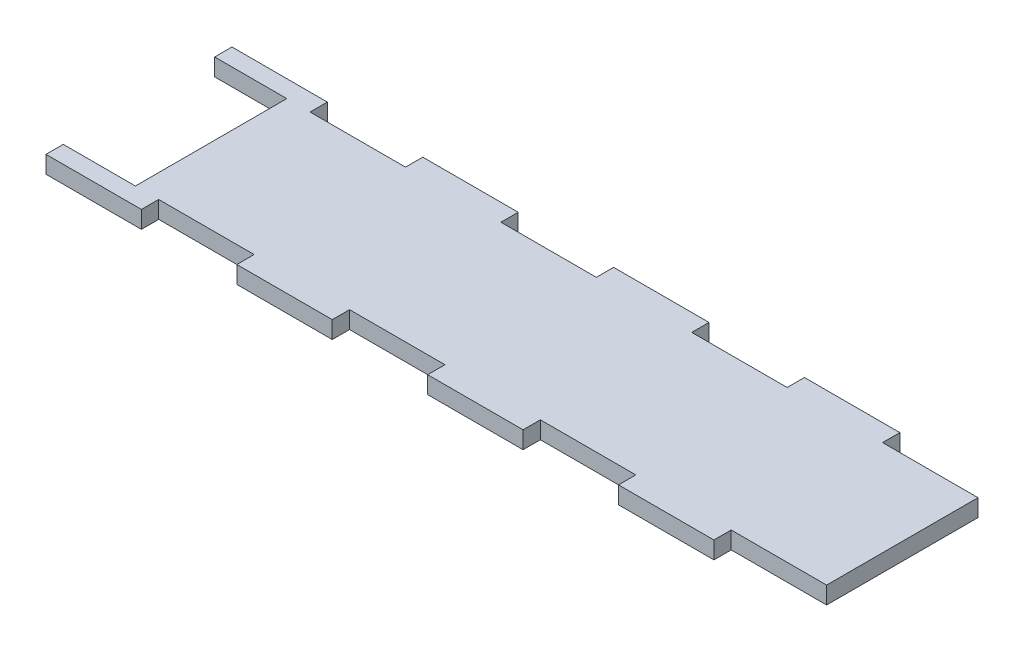
SolidWorks part; units mm, degrees
ref_plane "Front Plane" through (0, 0, 0) normal (0, 0, 1) x (1, 0, 0)
ref_plane "Top Plane" through (0, 0, 0) normal (0, 1, 0) x (1, 0, 0)
ref_plane "Right Plane" through (0, 0, 0) normal (1, 0, 0) x (0, 0, -1)
sketch "Sketch1" plane through (0, 0, 0) normal (0, 1, 0) x (1, 0, 0)
  line L1 (0, 0) -> (228.6, 0)
  line L2 (0, 0) -> (0, 49.5)
  line L3 (0, 49.5) -> (228.6, 49.5)
  line L4 (228.6, 0) -> (228.6, 49.5)
  line L5 (0, 0) -> (228.6, 49.5) construction
  line L6 (0, 49.5) -> (228.6, 0) construction
  point P4 (114.3, 24.75)
  dimension "D1" = 228.6
  dimension "D2" = 49.5
extrude "Boss-Extrude1" add sketch "Sketch1" along normal blind 4.6
sketch "Sketch3" plane through (0, 4.6, 0) normal (0, 1, 0) x (1, 0, 0)
  line L0 (0, 0) -> (228.6, 0) construction
  line L1 (0, 4.6) -> (25.4, 4.6)
  line L2 (0, 4.6) -> (0, 0)
  line L3 (0, 0) -> (25.4, 0)
  line L4 (25.4, 4.6) -> (25.4, 0)
  line L5 (0, 4.6) -> (25.4, 0) construction
  line L6 (0, 0) -> (25.4, 4.6) construction
  line L7 (50.8, 4.6) -> (76.2, 4.6)
  line L8 (50.8, 4.6) -> (50.8, 0)
  line L9 (50.8, 0) -> (76.2, 0)
  line L10 (76.2, 4.6) -> (76.2, 0)
  line L11 (50.8, 4.6) -> (76.2, 0) construction
  line L12 (50.8, 0) -> (76.2, 4.6) construction
  line L13 (101.6, 4.6) -> (127, 4.6)
  line L14 (101.6, 4.6) -> (101.6, 0)
  line L15 (101.6, 0) -> (127, 0)
  line L16 (127, 4.6) -> (127, 0)
  line L17 (101.6, 4.6) -> (127, 0) construction
  line L18 (101.6, 0) -> (127, 4.6) construction
  line L19 (177.8, 4.6) -> (152.4, 4.6)
  line L20 (177.8, 4.6) -> (177.8, 0)
  line L21 (177.8, 0) -> (152.4, 0)
  line L22 (152.4, 4.6) -> (152.4, 0)
  line L23 (177.8, 4.6) -> (152.4, 0) construction
  line L24 (177.8, 0) -> (152.4, 4.6) construction
  line L25 (203.2, 4.6) -> (228.6, 4.6)
  line L26 (203.2, 4.6) -> (203.2, 0)
  line L27 (203.2, 0) -> (228.6, 0)
  line L28 (228.6, 4.6) -> (228.6, 0)
  line L29 (203.2, 4.6) -> (228.6, 0) construction
  line L30 (203.2, 0) -> (228.6, 4.6) construction
  line L31 (0, 49.5) -> (0, 0) construction
  line L32 (228.6, 0) -> (228.6, 49.5) construction
  line L33 (25.4, 0) -> (50.8, 0) construction
  line L34 (76.2, 0) -> (101.6, 0) construction
  line L35 (127, 0) -> (152.4, 0)
  line L36 (177.8, 0) -> (203.2, 0)
  point P4 (12.7, 2.3)
  point P9 (63.5, 2.3)
  point P14 (114.3, 2.3)
  point P19 (165.1, 2.3)
  point P24 (215.9, 2.3)
  line M25 (0, 49.5) -> (0, 0)
  line M26 (0, 0) -> (228.6, 0)
  dimension "D1" = 0
  dimension "D2" = 0
  dimension "D3" = 4.6
  dimension "D4" = 25.4
  dimension "D5" = 25.4
extrude "Cut-Extrude1" cut sketch "Sketch3" against normal through all contours L4 L1 M25 M26 | L10 L7 L8 M26 | L16 L13 L14 M26 | L19 L22 L20 M26 | L26 L25 L28 L27 region at (165.1, 4.6, -2.3) region at (114.3, 4.6, -2.3) region at (63.5, 4.6, -2.3) region at (12.7, 4.6, -2.3)
ref_plane "Plane1" through (0, 0, -24.75) normal (0, 0, -1) x (-1, 0, 0)
mirror "Mirror1" about plane through (0, 0, -24.75) normal (0, 0, -1) of "Cut-Extrude1"
ref_plane "Plane2" through (0, 0, -24.75) normal (0, 0, 1) x (1, 0, 0)
sketch "Sketch4" plane through (0, 4.6, 0) normal (0, 1, 0) x (1, 0, 0)
  line L10 (50.8, 4.6) -> (76.2, 4.6) construction
  line L11 (0, 44.9) -> (45.1, 44.9)
  line L13 (0, 44.9) -> (0, 4.6)
  line L15 (0, 4.6) -> (45.1, 4.6)
  line L16 (45.1, 44.9) -> (45.1, 4.6)
  line L17 (0, 44.9) -> (45.1, 4.6) construction
  line L18 (0, 4.6) -> (45.1, 44.9) construction
  point P4 (22.55, 24.75)
extrude "Cut-Extrude5" [suppressed] cut sketch "Sketch4" against normal through all
sketch "Sketch7" plane through (0, 4.6, 0) normal (0, 1, 0) x (1, 0, 0)
  line L6 (0, 44.9) -> (0, 4.6) construction
  line L7 (4.6, 4.6) -> (44.6, 4.6) construction
  line L8 (4.6, 4.6) -> (4.6, 44.9) construction
  line L9 (4.6, 44.9) -> (44.6, 44.9) construction
  line L10 (44.6, 4.6) -> (44.6, 44.9) construction
  line L11 (0, 44.9) -> (25.4, 44.9) construction
  dimension "D3" = 4.6
  dimension "D1" = 40
  dimension "D2" = 40.3
  dimension "D4" = 0
sketch "Sketch8" plane through (0, 4.6, 0) normal (0, 1, 0) x (1, 0, 0)
  line L1 (44.6, 4.6) -> (0, 4.6)
  line L2 (44.6, 4.6) -> (44.6, 44.9)
  line L3 (44.6, 44.9) -> (0, 44.9)
  line L4 (0, 4.6) -> (0, 44.9)
extrude "Cut-Extrude6" cut sketch "Sketch8" against normal through all
equation "\"MDF\"= 4.8mm"
equation "\"Foamcore\"= 4.6mm"
equation "\"PCB\" = 1.6mm"
equation "\"GMaterial\"= \"MDF\""
equation "\"BaseWidth\" = 10in"
equation "\"SkidLength\" = 1in"
equation "\"SkidClearance\" = 0.4in"
equation "\"MotorMountLength\" = 2in"
equation "\"MotorMountWidth\" = \"GMaterial\""
equation "\"MotorMountHeight\" = 2.25in"
equation "\"UnoStackWidth\" = 77.4mm"
equation "\"UnoStackLength\" = 79.8mm"
equation "\"UnoStackHeight\" = 34.2mm"
equation "\"TallHexRiserHeight\" = 22.2mm"
equation "\"PingPongBallSize\" = 40mm"
equation "\"D1@Boss-Extrude1\"=\"Foamcore\""
equation "\"BarrelLength\" = 9in"
equation "\"BarrelSize\" = \"PingPongBallSize\""
equation "\"D1@Sketch1\"= \"BarrelLength\""
equation "\"D3@Sketch3\"=\"Foamcore\""
equation "\"PlatformLength\" = 4in"
equation "\"PlatformWidth\" = 6in"
equation "\"WheelDiameter\"=2.99213"
equation "\"ServoMountHeight\"=2.49223"
equation "\"ServoGearHeight\" = 0.95330261in"
equation "\"ServoMountLength\"= 1.53774"
equation "\"PivotHoleRadius\"= 0.616358"
equation "\"PlatformMountHeight\" = 3.19"
equation "\"TensionOffSet\"= .3mm"
equation "\"MotorMountWedge\"=0.333333"
equation "\"LaserCutterOffset\"= .3mm"
equation "\"BumperWidth\"=11"
equation "\"PitcherWheelCompression\" = 2.5mm"
equation "\"PitchingWheelWidth\" = 26.2mm"
equation "\"PitchingWheelDiameter\" = 65.5mm"
equation "\"PitchingWheelMountOffset\" = 8.4mm"
equation "\"PitchingWheelInnerDiameter\" = 45.5mm"
equation "\"PitchingWheelBoltShoulder\" = 4.5mm"
equation "\"BrassCouplingLength\" = 18mm"
equation "\"PitchingMotorHeight\" = 57.0mm"
equation "\"PitchingMotorShaftTopHeight\" = \"PitchingMotorHeight\" - 44.1mm"
equation "\"PitchingMotorBodyHeight\" = 38mm"
equation "\"PitchingMotorTopShoulderHeight\" = 40.6mm - \"PitchingMotorBodyHeight\" "
equation "\"PitchingMotorBottomShoulderHeight\" = 40.2mm - \"PitchingMotorBodyHeight\""
equation "\"PitchingMotorBottomShaftHeight\" = \"PitchingMotorHeight\" - \"PitchingMotorShaftTopHeight\" - \"PitchingMotorTopShoulderHeight\" - \"PitchingMotorBodyHeight\" - \"PitchingMotorBottomShoulderHeight\""
equation "\"PitchingMotorShaftDiameter\" = 2.2mm"
equation "\"PitchingMotorBodyDiameter\" = 27.4mm"
equation "\"PitchingMotorTopShoulderDiameter\" = 9.8mm"
equation "\"PitchingMotorBottomShoulderDiameter\" = 9.8mm"
equation "\"BrassCouplingHexSize\" = 12mm"
equation "\"BrassCouplingBoreSize\" = 3.17mm"
equation "\"PitchingMotorMountingHoleDistance\" = 16mm"
equation "\"Acrylic\" = 4.4mm"
equation "\"PitchingMotorDistance\" = \"PitchingWheelDiameter\" + \"PingPongBallSize\" - \"PitcherWheelCompression\"*2"
equation "\"PitchingMotorPlatformOffset\"=1"
equation "\"ServoPlatformOffset\"=1.64173"
equation "\"BallBearingDiameter\" = 22mm"
equation "\"BallBearingWidth\" = 9mm"
equation "\"BallBearingHexShoulder\" = 9mm - 5.9mm"
equation "\"BallBearingHexSize\" = .36in"
equation "\"PlatformMountFootLength\"=0.857143"
equation "\"WheelWidth\"= 26mm"
equation "\"ServoMountReductionBackHeight\"=2.25"
equation "\"PlatformBottomWidthThird\" =  0.857143in"
equation "\"PlatformMountBackReductionHeight\"= 2.5in"
equation "\"PlatformMountBackReductionWidth\"= 3/7in"
equation "\"PlatformMountFrontReductionWidth\" =  1.46226in"
equation "\"PlatformMountFrontReductionHeight\" = 2.5in"
equation "\"D2@Sketch1\"=\"PingPongBallSize\"+\"LaserCutterOffset\"+\"Foamcore\"*2"
equation "\"D1@Sketch7\"=\"PingPongBallSize\""
equation "\"D2@Sketch7\"=\"PingPongBallSize\"+\"LaserCutterOffset\""
equation "\"D3@Sketch7\"=\"Foamcore\""
